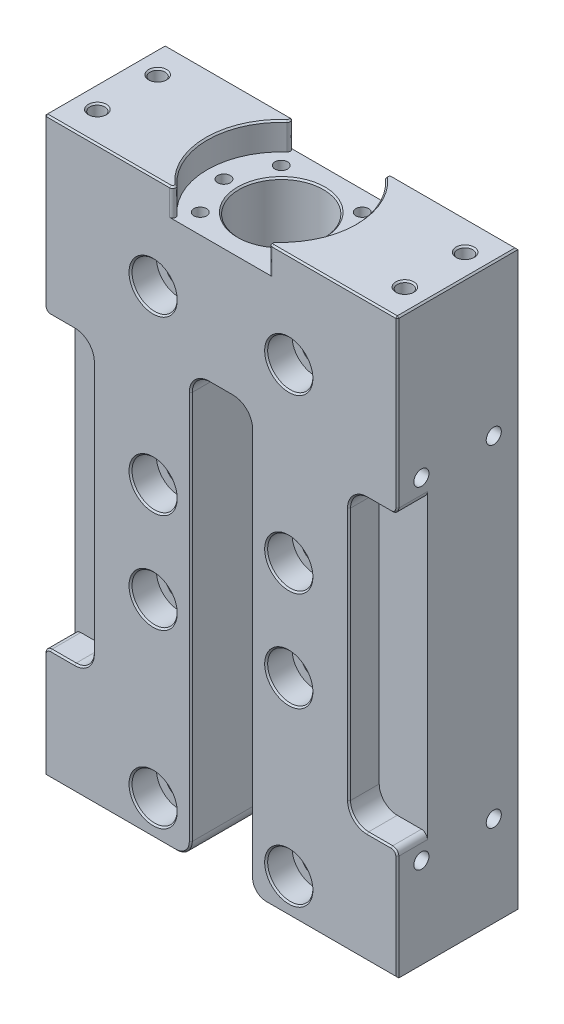
SolidWorks part; units mm, degrees
material "Alumina"
ref_plane "Plan de face" through (0, 0, 0) normal (0, 0, 1) x (1, 0, 0)
ref_plane "Plan de dessus" through (0, 0, 0) normal (0, 1, 0) x (1, 0, 0)
ref_plane "Plan de droite" through (0, 0, 0) normal (1, 0, 0) x (0, 0, -1)
sketch "Esquisse1" plane through (0, 0, 0) normal (0, 0, 1) x (1, 0, 0)
  line L0 (-10, -85) -> (-58.5, -85)
  line L1 (58.5, -85) -> (10, -85)
  line L2 (58.5, -85) -> (58.5, -48)
  line L3 (58.5, 105) -> (-58.5, 105)
  line L4 (-58.5, -85) -> (-58.5, -48)
  line L5 (58.5, -85) -> (-58.5, 105) construction
  line L6 (58.5, 105) -> (-58.5, -85) construction
  line L7 (58.5, 48) -> (58.5, 105)
  line L8 (-10, -85) -> (-10, 55)
  line L9 (-10, 55) -> (10, 55)
  line L10 (10, -85) -> (10, 55)
  line L11 (-58.5, 48) -> (-42.5, 48)
  line L12 (-58.5, -48) -> (-58.5, 48)
  line L13 (-58.5, -48) -> (-42.5, -48)
  line L14 (-42.5, 48) -> (-42.5, -48)
  line L15 (58.5, -48) -> (42.5, -48)
  line L16 (-58.5, 48) -> (-58.5, 105)
  line L17 (58.5, 48) -> (42.5, 48)
  line L18 (42.5, -48) -> (42.5, 48)
  line L19 (58.5, 48) -> (58.5, -48)
  point P0 (0, 10)
  dimension "D1" = 117
  dimension "D2" = 190
  dimension "D3" = 20
  dimension "D4" = 10
  dimension "D5" = 140
  dimension "D6" = 10
  dimension "D7" = 96
  dimension "D8" = 37
  dimension "D9" = 16
  dimension "D10" = 16
  dimension "D11" = 96
extrude "Boss.-Extru.1" add sketch "Esquisse1" along normal blind 40 contours L15 L18 L17 L7 L3 L16 L11 L14 L13 L4 L0 L8 L9 L10 L1 L2 region at (-34.25, -82.7687, 0)
extrude "Boss-Extrude1" add sketch "Esquisse1<4>" along normal blind 30 contours L14 L11 L12 L13 | L19 L17 L18 L15 region at (-50.5, 0, 0) region at (50.5, 0, 0)
sketch "Esquisse1<4>" plane through (0, 0, 0) normal (0, 0, 1) x (1, 0, 0) same geometry as "Esquisse1"
sketch "Esquisse3" plane through (0, 105, 0) normal (0, 1, 0) x (1, 0, 0)
  line L1 (58.5, 0) -> (-58.5, 0) construction
  circle A0 centre (0, -20) radius 14
  dimension "D1" = 20
  dimension "D2" = 28
extrude "Enlèv. mat.-Extru.2" cut sketch "Esquisse3" against normal blind 40
fillet "Congé1" radius 6 2 edges at (10, 55, 20) (-10, 55, 20)
hole_wizard "CBORE for M8 Hex Socket Head Cap Screw2" positions "Sketch5" profile "Sketch6" counterbore size "M8" standard "ISO" end condition through all
sketch "Sketch5" plane through (0, 0, 40) normal (0, 0, 1) x (1, 0, 0)
  point P0 (-22.5, 73.5)
  point P3 (22.5, 73.5)
  point P6 (22.5, 16.5)
  point P9 (-22.5, 16.5)
  point P12 (-22.5, -16.5)
  point P15 (22.5, -16.5)
  point P18 (22.5, -73.5)
  point P21 (-22.5, -73.5)
sketch "Sketch6" plane through (-22.5, 73.5, 40) normal (1, 0, 0) x (0, -1, 0)
  line L0 (0, 0) -> (0, 40)
  line L1 (0, 40) -> (4.5, 40)
  line L3 (4.5, 40) -> (4.5, 8.6)
  line L4 (4.5, 8.6) -> (7.5, 8.6)
  line L5 (7.5, 8.6) -> (7.5, 0)
  line L7 (7.5, 0) -> (0, 0)
  line L11 (0, -6.35) -> (0, 107.95) construction
  dimension "Thru Hole Dia." = 9
  dimension "Thru Hole Depth" = 40
  dimension "C'Bore Dia." = 15
  dimension "C'Bore Depth" = 8.6
sketch "Sketch7" plane through (0, 105, 0) normal (0, 1, 0) x (1, 0, 0)
  circle A0 centre (0, -20) radius 24.5
extrude "Cut-Extrude2" cut sketch "Sketch7" against normal blind 9
hole_wizard "M5 Tapped Hole2" positions "Sketch10" profile "Sketch11" tap size "M5" standard "ISO"
sketch "Sketch10" plane through (0, 96, 0) normal (0, 1, 0) x (1, 0, 0)
  point P0 (-13.435, -6.565)
  point P3 (-19, -20)
  point P6 (13.435, -6.565)
  point P9 (19, -20)
  point P12 (13.435, -33.435)
  point P15 (-13.435, -33.435)
sketch "Sketch11" plane through (-13.435, 96, 6.565) normal (1, 0, 0) x (0, 0, 1)
  line L0 (0, 0) -> (0, 15.2618)
  line L1 (0, 15.2618) -> (2.1, 14)
  line L2 (2.1, 14) -> (2.1, 0)
  line L5 (2.1, 0) -> (0, 0)
  line L10 (0, 15.2618) -> (-2.1, 14) construction
  line L11 (0, -6.35) -> (0, 107.95) construction
  dimension "Tap Drill Dia." = 4.2
  dimension "Tap Drill Depth" = 14
  dimension "Drill Angle" = 118
cosmetic thread "Hole Thread7" parameters "D1"=10, "D2"=5
cosmetic thread "Hole Thread8" parameters "D1"=10, "D2"=5
cosmetic thread "Hole Thread9" parameters "D1"=10, "D2"=5
cosmetic thread "Hole Thread10" parameters "D1"=10, "D2"=5
cosmetic thread "Hole Thread11" parameters "D1"=10, "D2"=5
cosmetic thread "Hole Thread12" parameters "D1"=10, "D2"=5
sketch "Sketch12" plane through (0, 65, 0) normal (0, 1, 0) x (1, 0, 0)
  circle A0 centre (0, -20) radius 9
  dimension "D1" = 18
extrude "Cut-Extrude3" cut sketch "Sketch12" against normal through all
hole_wizard "Tap Drill for M6 Tap2" positions "Sketch13" profile "Sketch14" hole size "M6" standard "ISO"
sketch "Sketch13" plane through (58.5, 0, 0) normal (1, 0, 0) x (0, 0, -1)
  line L5 (-40, 105) -> (0, 105) construction
  point P0 (-8, 55)
  point P3 (-32, 55)
  point P6 (-8, -55)
  point P9 (-32, -55)
  dimension "D1" = 24
  dimension "D2" = 110
  dimension "D3" = 50
sketch "Sketch14" plane through (58.5, 55, 8) normal (0, 1, 0) x (0, 0, -1)
  line L0 (0, 0) -> (0, 11.5022)
  line L1 (0, 11.5022) -> (2.5, 10)
  line L2 (2.5, 10) -> (2.5, 0)
  line L5 (2.5, 0) -> (0, 0)
  line L10 (0, 11.5022) -> (-2.5, 10) construction
  line L11 (0, -6.35) -> (0, 107.95) construction
  dimension "Hole Dia." = 5
  dimension "Hole Depth" = 10
  dimension "Drill Angle" = 118
mirror "Mirror1" about plane through (0, 0, 0) normal (1, 0, 0) of "Tap Drill for M6 Tap2"
fillet "Fillet2" radius 5 2 edges at (10, -85, 20) (-10, -85, 20)
fillet "Fillet3" radius 6 4 edges at (-42.5, 48, 35) (-42.5, -48, 35) (42.5, -48, 35) (42.5, 48, 35)
fillet "Fillet4" radius 2 4 edges at (58.5, -48, 35) (58.5, 48, 35) (-58.5, -48, 35) (-58.5, 48, 35)
hole_wizard "Tap Drill for M6 Tap1" positions "Sketch16" profile "Sketch17" hole size "M6" standard "ISO"
sketch "Sketch16" plane through (0, 105, 0) normal (0, 1, 0) x (1, 0, 0)
  line L0 (-58.5, -40) -> (-58.5, 0) construction
  line L1 (-14.151, -40) -> (-58.5, -40) construction
  line L2 (58.5, -40) -> (58.5, 0) construction
  point P0 (-51, -30)
  point P2 (-51, -10)
  point P4 (51, -10)
  point P6 (51, -30)
  dimension "D1" = 7.5
  dimension "D2" = 20
  dimension "D3" = 10
  dimension "D4" = 7.5
sketch "Sketch17" plane through (-51, 105, 30) normal (1, 0, 0) x (0, 0, 1)
  line L0 (0, 0) -> (0, 24.5022)
  line L1 (0, 24.5022) -> (2.5, 23)
  line L2 (2.5, 23) -> (2.5, 0)
  line L5 (2.5, 0) -> (0, 0)
  line L10 (0, 24.5022) -> (-2.5, 23) construction
  line L11 (0, -6.35) -> (0, 107.95) construction
  dimension "Hole Dia." = 5
  dimension "Hole Depth" = 23
  dimension "Drill Angle" = 118
fillet "Fillet1" radius 1 4 edges at (14.151, 100.5, 40) (-14.151, 100.5, 40) (-14.151, 100.5, 0) (14.151, 100.5, 0)
chamfer "Chamfer1" distance 0.5 angle 45 52 edges at (-36.75, -85, 40) (-11.4645, -83.5355, 40) (-10, -15.5, 40) (-8.2426, 53.2426, 40) (0, 55, 40) (8.2426, 53.2426, 40) (10, -15.5, 40) (11.4645, -83.5355, 40) (36.75, -85, 40) (58.5, -67.5, 40) (58.5, 77.5, 40) (57.9142, -48.5858, 40) (57.9142, 48.5858, 40) (52.5, -48, 40) (52.5, 48, 40) (44.2574, -46.2426, 40) (44.2574, 46.2426, 40) (42.5, 0, 40) (-58.5, 77.5, 40) (-58.5, -67.5, 40) (-57.9142, 48.5858, 40) (-57.9142, -48.5858, 40) (-52.5, 48, 40) (-52.5, -48, 40) (-44.2574, 46.2426, 40) (-44.2574, -46.2426, 40) (-42.5, 0, 40) (-37.7537, 105, 40) (37.7537, 105, 40) (-37.7537, 105, 0) (-16.0732, 105, 0.643) (-24.5, 105, 20) (-16.0732, 105, 39.357) (37.7537, 105, 0) (16.0732, 105, 0.643) (24.5, 105, 20) (16.0732, 105, 39.357) (-14, 96, 20) (51, 105, 32.5) (51, 105, 12.5) (-51, 105, 32.5) (-51, 105, 12.5) (-58.5, 105, 20) (58.5, 105, 20) (-15, -73.5, 40) (30, -73.5, 40) (30, -16.5, 40) (30, 16.5, 40) (-15, -16.5, 40) (-15, 16.5, 40) (-15, 73.5, 40) (30, 73.5, 40)
